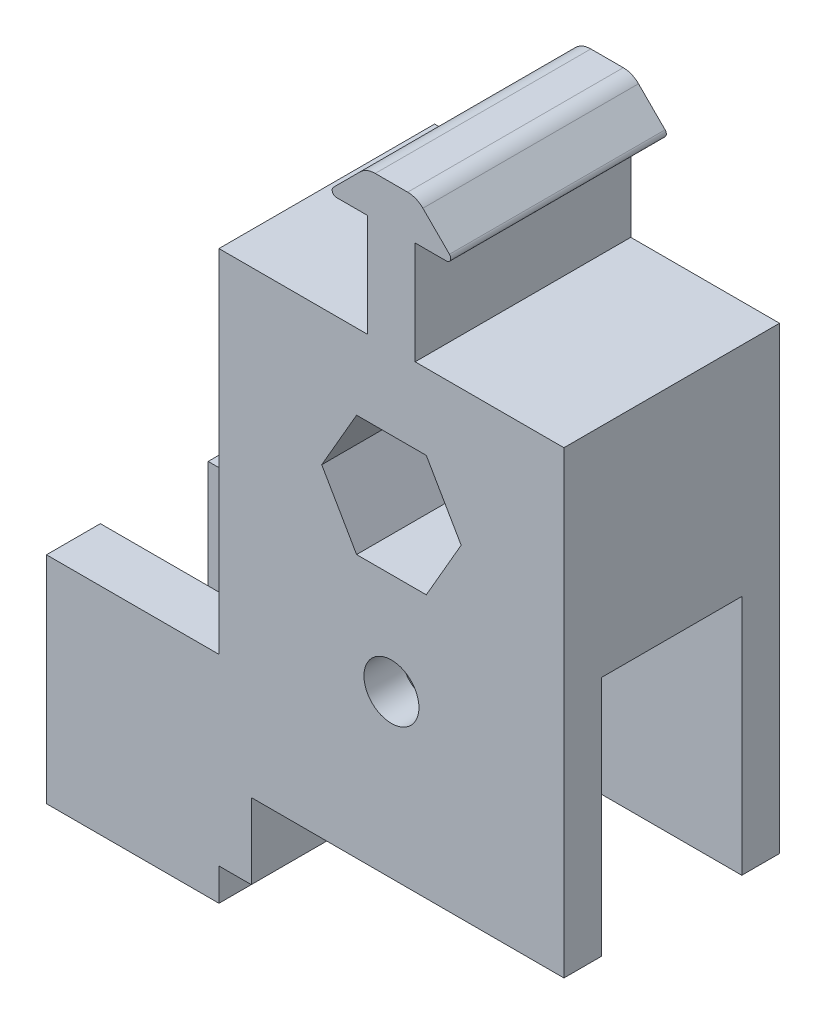
SolidWorks part; units mm, degrees
ref_plane "Front Plane" through (0, 0, 0) normal (0, 0, 1) x (1, 0, 0)
ref_plane "Top Plane" through (0, 0, 0) normal (0, 1, 0) x (1, 0, 0)
ref_plane "Right Plane" through (0, 0, 0) normal (1, 0, 0) x (0, 0, -1)
sketch "Sketch1" plane through (0, 0, 0) normal (0, 0, 1) x (1, 0, 0)
  line L0 (-20.32, 16.002) -> (-20.32, -38.1)
  line L1 (-4.1061, 7.112) -> (-8.2122, 0)
  line L2 (-8.2122, 0) -> (-4.1061, -7.112)
  line L3 (-4.1061, -7.112) -> (4.1061, -7.112)
  line L4 (4.1061, -7.112) -> (8.2122, 0)
  line L5 (8.2122, 0) -> (4.1061, 7.112)
  line L6 (4.1061, 7.112) -> (-4.1061, 7.112)
  line L7 (-20.32, -38.1) -> (20.32, -38.1)
  line L8 (20.32, -38.1) -> (20.32, 16.002)
  line L9 (-20.32, 16.002) -> (-2.794, 16.002)
  line L10 (-2.794, 16.002) -> (-2.794, 28.1305)
  line L11 (-2.794, 28.1305) -> (-6.477, 28.1305)
  line L12 (-6.8362, 28.9977) -> (-3.7065, 32.1275)
  line L13 (-1.9104, 32.8714) -> (1.9104, 32.8714)
  line L14 (0, 41.8096) -> (0, -25.778) construction
  line L15 (20.32, 16.002) -> (2.794, 16.002)
  line L16 (2.794, 16.002) -> (2.794, 28.1305)
  line L17 (6.8362, 28.9977) -> (3.7065, 32.1275)
  line L18 (2.794, 28.1305) -> (6.477, 28.1305)
  line L19 (-6.985, 28.6385) -> (6.985, 28.6385) construction
  circle A0 centre (0, 0) radius 7.112 construction
  arc A1 (-6.477, 28.1305) -> (-6.8362, 28.9977) centre (-6.477, 28.6385) cw
  arc A2 (-3.7065, 32.1275) -> (-1.9104, 32.8714) centre (-1.9104, 30.3314) cw
  arc A3 (3.7065, 32.1275) -> (1.9104, 32.8714) centre (1.9104, 30.3314) ccw
  arc A4 (6.477, 28.1305) -> (6.8362, 28.9977) centre (6.477, 28.6385) ccw
  point P18 (7.7034, 28.1305)
  point P21 (-4.6355, 28.1305)
  point P25 (-7.7034, 28.1305)
  point P29 (0, -38.1)
  point P35 (0, 32.8714)
  dimension "D7" = 0.508
  dimension "D8" = 2.54
  dimension "D1" = 14.224
  dimension "D2" = 21.0185
  dimension "D3" = 5.588
  dimension "D4" = 4.7409
  dimension "D5" = 135
  dimension "D6" = 13.97
  dimension "D9" = 38.1
  dimension "D10" = 8.89
  dimension "D11" = 20.32
extrude "Boss-Extrude1" add sketch "Sketch1" along normal mid plane 25.4
sketch "Sketch10" plane through (0, 0, 0) normal (0, 0, 1) x (1, 0, 0)
  line L0 (-20.32, -38.1) -> (-20.32, -46.99)
  line L1 (-20.32, -46.99) -> (-40.64, -46.99)
  line L2 (-40.64, -46.99) -> (-40.64, -50.8)
  line L3 (-40.64, -50.8) -> (-16.51, -50.8)
  line L4 (-16.51, -50.8) -> (-16.51, -38.1)
  line L5 (-20.32, -38.1) -> (20.32, -38.1) construction
  line L6 (-20.32, -38.1) -> (-16.51, -38.1)
  dimension "D2" = 8.89
  dimension "D3" = 3.81
  dimension "D4" = 20.32
extrude "Boss-Extrude4" add sketch "Sketch10" along normal up to surface and the other way up to surface up to face at (0, 18.0275, 12.7) other way up to face at (0, 18.0275, -12.7)
sketch "Sketch6" plane through (20.32, 0, 0) normal (1, 0, 0) x (0, 0, -1)
  line L0 (-12.7, -7.112) -> (12.7, -7.112) construction
  line L1 (-12.7, -7.112) -> (12.7, -7.112) construction
  line L2 (-8.255, -25.4) -> (-8.255, -9.652)
  line L3 (-8.255, -9.652) -> (8.255, -9.652)
  line L11 (-8.255, -25.4) -> (8.255, -25.4)
  line L12 (8.255, -9.652) -> (8.255, -25.4)
  point P10 (0, -9.652)
  dimension "D2" = 16.51
  dimension "D3" = 2.54
  dimension "D1" = 15.748
extrude "Cut-Extrude2" cut sketch "Sketch6" against normal through all
sketch "Sketch11" plane through (0, -46.99, 0) normal (0, 1, 0) x (1, 0, 0)
  line L0 (-40.64, -12.7) -> (-40.64, 12.7) construction
  line L1 (-20.32, -12.7) -> (-20.32, 12.7) construction
  line L2 (-40.64, -3.81) -> (-40.64, 3.81)
  line L3 (-20.32, -3.81) -> (-20.32, 3.81)
  line L4 (-40.64, 3.81) -> (-20.32, 3.81)
  line L5 (-40.64, -3.81) -> (-20.32, -3.81)
  point P8 (-20.32, 0)
  point P9 (-40.64, 0)
  dimension "D1" = 7.62
extrude "Cut-Extrude3" cut sketch "Sketch11" against normal up to surface (3.81 mm away) up to face at (-28.575, -50.8, 0)
sketch "Sketch15" plane through (0, 0, 12.7) normal (0, 0, 1) x (1, 0, 0)
  line L1 (-4.1061, -7.112) -> (4.1061, -7.112) construction
  circle A0 centre (0, -19.05) radius 3.2385
  point P7 (0, -7.112)
  dimension "D1" = 6.477
  dimension "D2" = 11.938
extrude "Cut-Extrude4" cut sketch "Sketch15" against normal up to surface (25.4 mm away) up to face at (-5.715, 4.643, -12.7)
sketch "Sketch16" plane through (20.32, 0, 0) normal (1, 0, 0) x (0, 0, -1)
  line L0 (-8.255, -25.4) -> (8.255, -25.4) construction
  line L1 (-8.255, -25.4) -> (8.255, -25.4)
  line L2 (-8.255, -25.4) -> (-8.255, -38.1)
  line L3 (-12.7, -38.1) -> (12.7, -38.1) construction
  line L4 (-8.255, -38.1) -> (8.255, -38.1)
  line L5 (8.255, -38.1) -> (8.255, -25.4)
extrude "Cut-Extrude5" cut sketch "Sketch16" against normal up to surface (36.83 mm away) up to face at (-16.51, -44.45, 0)
sketch "Sketch17" plane through (-20.32, 0, 0) normal (-1, 0, 0) x (0, 0, 1)
  line L0 (12.7, 16.002) -> (12.7, -46.99) construction
  line L1 (-3.81, -50.8) -> (-3.81, -46.99) construction
  line L2 (-3.81, -46.99) -> (-12.7, -46.99) construction
  line L3 (3.81, -50.8) -> (3.81, -46.99) construction
  line L4 (12.7, -46.99) -> (3.81, -46.99) construction
  line L5 (-3.81, -50.8) -> (3.81, -50.8) construction
  line L6 (-12.7, 16.002) -> (-12.7, -46.99) construction
  line L7 (12.7, -25.4) -> (12.7, -46.99)
  line L8 (-3.81, -50.8) -> (-3.81, -46.99)
  line L9 (-3.81, -46.99) -> (-12.7, -46.99)
  line L10 (3.81, -50.8) -> (3.81, -46.99)
  line L11 (12.7, -46.99) -> (3.81, -46.99)
  line L12 (-3.81, -50.8) -> (3.81, -50.8)
  line L13 (-12.7, -25.4) -> (-12.7, -46.99)
  line L14 (-12.7, -25.4) -> (12.7, -25.4)
  dimension "D1" = 21.59
extrude "Boss-Extrude5" add sketch "Sketch17" along normal blind 5.08
sketch "Sketch18" plane through (-25.4, 0, 0) normal (-1, 0, 0) x (0, 0, 1)
  line L0 (0, 0) -> (0, -56.8096) construction
  line L1 (-3.81, -46.99) -> (-12.7, -46.99) construction
  line L2 (-12.7, -25.4) -> (-12.7, -46.99) construction
  line L4 (-6.35, -46.99) -> (-12.7, -46.99)
  line L5 (-12.7, -25.4) -> (-12.7, -46.99)
  line L6 (12.7, -25.4) -> (-12.7, -25.4) construction
  line L7 (-6.35, -25.4) -> (-6.35, -46.99)
  line L8 (-6.35, -25.4) -> (-12.7, -25.4)
  line L9 (6.35, -25.4) -> (12.7, -25.4)
  line L10 (6.35, -25.4) -> (6.35, -46.99)
  line L11 (12.7, -25.4) -> (12.7, -46.99)
  line L12 (6.35, -46.99) -> (12.7, -46.99)
  dimension "D1" = 6.35
extrude "Boss-Extrude6" add sketch "Sketch18" along normal up to surface (15.24 mm away) up to face at (-40.64, -48.895, 8.255)
sketch "Sketch22" plane through (0, 0, 12.7) normal (0, 0, 1) x (1, 0, 0)
  line L0 (-20.32, -50.8) -> (-20.32, -46.99)
  line L1 (-16.51, -50.8) -> (-40.64, -50.8) construction
  line L2 (-20.32, -46.99) -> (-16.51, -46.99)
  line L4 (-16.51, -50.8) -> (-20.32, -50.8)
  line L5 (-16.51, -38.1) -> (-16.51, -50.8) construction
  line L6 (-16.51, -46.99) -> (-16.51, -50.8)
  point P4 (0, 0)
  point P6 (-16.51, -44.9409)
  point P7 (-16.51, -49.1876)
  point P8 (-16.838, -45.9353)
  point P9 (0, 0)
  point P10 (-17.78, -50.8)
  point P11 (-20.0025, -50.8)
  point P12 (-16.51, -44.9341)
  dimension "D1" = 3.81
  dimension "D2" = 3.81
extrude "Cut-Extrude6" cut sketch "Sketch22" against normal up to surface (25.4 mm away) up to face at (-5.715, 6.802, -12.7)
